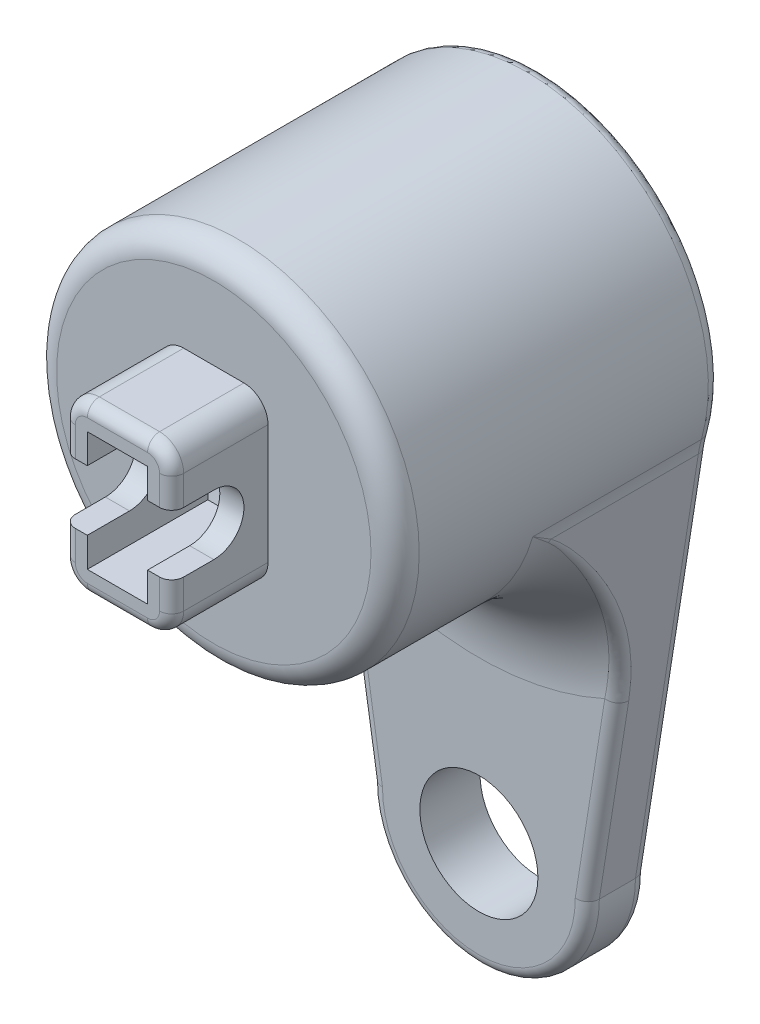
SolidWorks part; units mm, degrees
ref_plane "Front Plane" through (0, 0, 0) normal (0, 0, 1) x (1, 0, 0)
ref_plane "Top Plane" through (0, 0, 0) normal (0, 1, 0) x (1, 0, 0)
ref_plane "Right Plane" through (0, 0, 0) normal (1, 0, 0) x (0, 0, -1)
sketch "Sketch1" plane through (0, 0, 0) normal (0, 0, 1) x (1, 0, 0)
  circle A0 centre (0, 0) radius 13.05
  circle A1 centre (0, 0) radius 15.05
extrude "Boss-Extrude1" add sketch "Sketch1" along normal blind 25
sketch "Sketch2" plane through (0, 0, 0) normal (0, 0, 1) x (1, 0, 0)
  line L1 (-2.5, -4.95) -> (2.5, -4.95)
  line L2 (-2.5, -4.95) -> (-2.5, 4.95)
  line L3 (-2.5, 4.95) -> (2.5, 4.95)
  line L4 (2.5, -4.95) -> (2.5, 4.95)
  line L5 (-2.5, -4.95) -> (2.5, 4.95) construction
  line L6 (-2.5, 4.95) -> (2.5, -4.95) construction
  circle A0 centre (0, 0) radius 15.05
extrude "Boss-Extrude2" add sketch "Sketch2" along normal blind 2 from surface starting at face at (15.05, 0, 25)
sketch "Sketch3" plane through (0, 0, 0) normal (0, 0, 1) x (1, 0, 0)
  line L0 (13.05, 0) -> (15.05, 0)
  line L1 (-15.05, 0) -> (-13.05, 0)
  line L5 (0, -15.05) -> (0, -38.4059) construction
  line L6 (-15.05, 0) -> (-9, -38.4059)
  line L7 (15.05, 0) -> (9, -38.4059)
  circle A0 centre (0, 0) radius 15.05 construction
  arc A1 (-13.05, 0) -> (13.05, 0) centre (0, 0) ccw
  circle A2 centre (0, -38.4059) radius 4.9
  arc A3 (-9, -38.4059) -> (9, -38.4059) centre (0, -38.4059) ccw
extrude "Boss-Extrude3" add sketch "Sketch3" along normal blind 5
fillet "Fillet1" radius 2 1 edges at (15.05, 0, 27)
fillet "Fillet2" radius 10 3 edges at (0, -15.05, 5) (14.3212, -4.6268, 2.5) (-14.3212, -4.6268, 2.5)
fillet "Fillet3" radius 1 1 edges at (13.05, 0, 25)
sketch "Sketch5" plane through (0, 0, 0) normal (0, 0, 1) x (1, 0, 0)
  line L5 (-2.5, -4.95) -> (2.5, -4.95)
  line L6 (-2.5, -4.95) -> (-2.5, 4.95)
  line L7 (-4.5, -6.95) -> (4.5, -6.95)
  line L8 (-4.5, -6.95) -> (-4.5, 6.95)
  line L9 (-4.5, 6.95) -> (4.5, 6.95)
  line L10 (4.5, -6.95) -> (4.5, 6.95)
  line L11 (-2.5, 4.95) -> (2.5, 4.95)
  line L12 (2.5, -4.95) -> (2.5, 4.95)
  line L13 (-2.5, -4.95) -> (2.5, 4.95) construction
  line L14 (-2.5, 4.95) -> (2.5, -4.95) construction
  point P0 (0, 0)
extrude "Boss-Extrude4" add sketch "Sketch5" along normal blind 8 from surface starting at face at (13.05, 0, 27)
fillet "Fillet4" radius 2 4 edges at (4.5, -6.95, 31) (-4.5, -6.95, 31) (-4.5, 6.95, 31) (4.5, 6.95, 31)
fillet "Fillet5" radius 1 14 edges at (13.4659, -10.0562, 9.3393) (-12.3263, -17.2902, 5.7567) (14.3271, -4.7069, 0) (-14.3271, -4.7069, 0) (10.2741, -30.3176, 5) (0, -47.4059, 5) (-10.2741, -30.3176, 5) (0, -47.4059, 0) (11.6074, -21.8538, 0) (-11.6074, -21.8538, 0) (0, 15.05, 0) (13.05, 0, 0)
fillet "Fillet6" radius 1 8 edges at (0, 6.95, 35) (-3.9142, 6.3642, 35) (-4.5, 0, 35) (-3.9142, -6.3642, 35) (0, -6.95, 35) (3.9142, -6.3642, 35) (3.9142, 6.3642, 35) (4.5, 0, 35)
sketch "Sketch8" plane through (0, 0, 0) normal (1, 0, 0) x (0, 0, -1)
  line L0 (-35, 0) -> (-31.5, 0) construction
  line L1 (-35, -4.95) -> (-35, 4.95) construction
  line L2 (-31.5, 2.5) -> (-35, 2.5)
  line L3 (-35, 2.5) -> (-35, -2.5)
  line L4 (-35, -2.5) -> (-31.5, -2.5)
  arc A0 (-31.5, -2.5) -> (-31.5, 2.5) centre (-31.5, 0) ccw
extrude "Cut-Extrude2" cut sketch "Sketch8" against normal through all both and the other way through all
